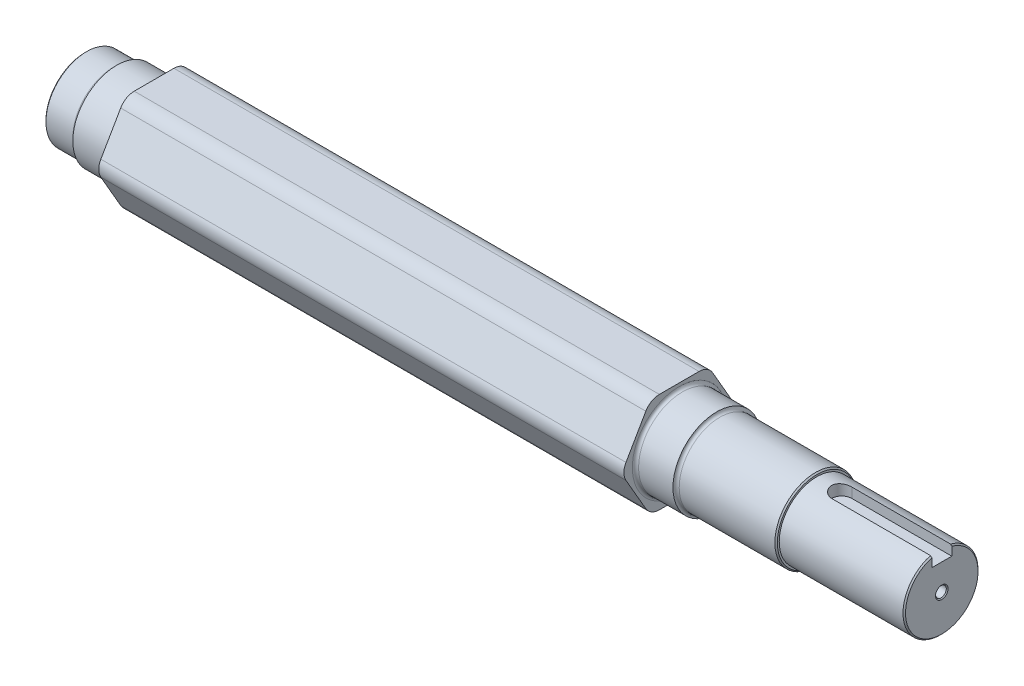
SolidWorks part; units mm, degrees
ref_plane "Front Plane" through (0, 0, 0) normal (0, 0, 1) x (1, 0, 0)
ref_plane "Top Plane" through (0, 0, 0) normal (0, 1, 0) x (1, 0, 0)
ref_plane "Right Plane" through (0, 0, 0) normal (1, 0, 0) x (0, 0, -1)
sketch "Sketch1" plane through (0, 0, 0) normal (1, 0, 0) x (0, 0, -1)
  line L0 (45.1934, 0) -> (-45.1934, 0) construction
  line L1 (23.094, -40) -> (46.188, 0)
  line L2 (46.188, 0) -> (23.094, 40)
  line L3 (23.094, 40) -> (-23.094, 40)
  line L4 (-23.094, 40) -> (-46.188, 0)
  line L5 (-46.188, 0) -> (-23.094, -40)
  line L6 (-23.094, -40) -> (23.094, -40)
  circle A0 centre (0, 0) radius 40 construction
  dimension "D1" = 80
extrude "Boss-Extrude3" add sketch "Sketch1" along normal mid plane 420
sketch "Sketch3" plane through (0, 0, 0) normal (0, 0, 1) x (1, 0, 0)
  line L0 (-210, 35) -> (-240, 35)
  line L1 (-210, 40) -> (-210, 0) construction
  line L2 (-240, 35) -> (-240, 32.5)
  line L3 (-240, 32.5) -> (-265, 32.5)
  line L4 (-265, 32.5) -> (-265, 0)
  line L5 (-265, 0) -> (-210, 0)
  line L6 (50.8068, 0) -> (-50.8068, 0) construction
  line L7 (-210, 0) -> (-210, 35)
  line L8 (210, 35) -> (240, 35)
  line L9 (210, 40) -> (210, 0) construction
  line L10 (240, 35) -> (240, 32.5)
  line L11 (240, 32.5) -> (320, 32.5)
  line L12 (320, 32.5) -> (320, 30)
  line L13 (320, 30) -> (420, 30)
  line L14 (420, 30) -> (420, 0)
  line L15 (420, 0) -> (210, 0)
  line L16 (210, 0) -> (210, 35)
  point P21 (315, 0)
  dimension "D1" = 30
  dimension "D2" = 80
  dimension "D3" = 100
  dimension "D4" = 30
  dimension "D5" = 32.5
  dimension "D6" = 35
  dimension "D7" = 25
  dimension "D8" = 30
  dimension "D9" = 32.5
revolve "Revolve1" add sketch "Sketch3" angle 360 about L5 other way angle 360
fillet "Fillet1" radius 2.5 4 edges at (-240, 0, 32.5) (-210, 0, 35) (240, 0, 32.5) (210, 0, 35)
fillet "Fillet2" radius 12.5 6 edges at (0, -40, -23.094) (0, 0, -46.188) (0, 40, -23.094) (0, -40, 23.094) (0, 0, 46.188) (0, 40, 23.094)
chamfer "Chamfer1" distance 1 angle 45 3 edges at (-265, 0, 32.5) (420, 0, 30) (320, 0, 32.5)
hole_wizard "M10 Tapped Hole1" positions "3DSketch1" profile "Sketch6" tap size "M10" standard "ISO"
sketch3d "3DSketch1"
  line L0 (-264, 0, 0) -> (-265, 0, 0) construction
  line L1 (419, 0, 0) -> (420, 0, 0) construction
  point P0 (-265, 0, 0)
  point P4 (420, 0, 0)
sketch "Sketch6" plane through (-265, 0, 0) normal (0, 1, 0) x (0, 0, 1)
  line L0 (0, 0) -> (0, 30.0537)
  line L1 (0, 30.0537) -> (4.25, 27.5)
  line L2 (4.25, 27.5) -> (4.25, 0.6503)
  line L3 (4.25, 0.6503) -> (5.025, 0)
  line L5 (5.025, 0) -> (0, 0)
  line L6 (-4.25, 0.6503) -> (-5.025, 0) construction
  line L10 (0, 30.0537) -> (-4.25, 27.5) construction
  line L11 (0, -6.35) -> (0, 107.95) construction
  dimension "Tap Drill Dia." = 8.5
  dimension "Tap Drill Depth" = 27.5
  dimension "Near C'Sink Dia." = 10.05
  dimension "Near C'Sink Angle" = 100
  dimension "Drill Angle" = 118
cosmetic thread "Hole Thread1" parameters "D1"=20, "D2"=10
cosmetic thread "Hole Thread2" parameters "D1"=20, "D2"=10
ref_plane "Plane1" through (0, 30, 0) normal (0, 1, 0) x (1, 0, 0)
sketch "Sketch7" plane through (0, 30, 0) normal (0, 1, 0) x (1, 0, 0)
  line L0 (420, 0) -> (340, 0) construction
  line L1 (420, -29) -> (420, 29) construction
  line L2 (-44, 0) -> (44, 0) construction
  line L3 (420, -8) -> (340, -8)
  line L4 (420, 8) -> (340, 8)
  arc A0 (420, -8) -> (420, 8) centre (420, 0) ccw
  arc A1 (340, 8) -> (340, -8) centre (340, 0) ccw
  point P7 (380, 0)
  dimension "D1" = 16
  dimension "D2" = 80
extrude "Cut-Extrude1" cut sketch "Sketch7" against normal blind 9
